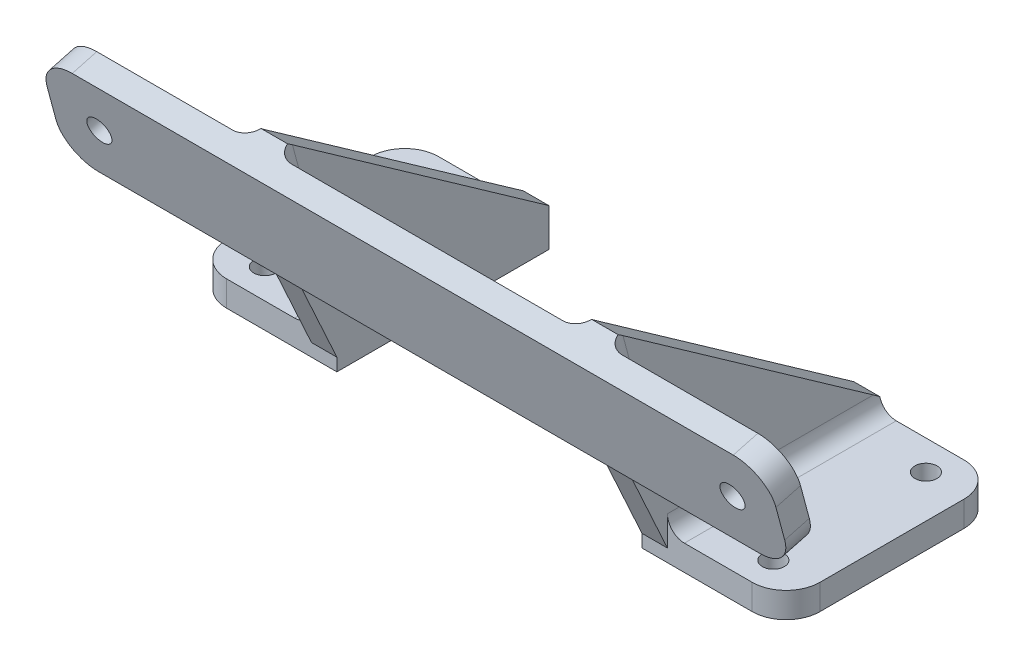
SolidWorks part; units mm, degrees
ref_plane "Front" through (0, 0, 0) normal (0, 0, 1) x (1, 0, 0)
ref_plane "Top" through (0, 0, 0) normal (0, 1, 0) x (1, 0, 0)
ref_plane "Right" through (0, 0, 0) normal (1, 0, 0) x (0, 0, -1)
ref_axis "X" through (-80.9, 0, 0) along (1, 0, 0)
ref_axis "Y" through (0, -50, 0) along (0, 1, 0)
ref_axis "Z" through (0, 0, -80.9) along (0, 0, 1)
sketch "Sketch1" plane through (0, 0, 0) normal (0, 1, 0) x (1, 0, 0)
  line L0 (-26.5, 16) -> (26.5, 16) construction
  line L1 (-35, 28.5) -> (-18, 28.5)
  line L2 (-35, 28.5) -> (-35, 3.5)
  line L3 (-35, 3.5) -> (-18, 3.5)
  line L4 (-18, 28.5) -> (-18, 3.5)
  line L5 (-35, 28.5) -> (-18, 3.5) construction
  line L6 (-35, 3.5) -> (-18, 28.5) construction
  line L7 (18, 28.5) -> (35, 28.5)
  line L8 (18, 28.5) -> (18, 3.5)
  line L9 (18, 3.5) -> (35, 3.5)
  line L10 (35, 28.5) -> (35, 3.5)
  line L11 (18, 28.5) -> (35, 3.5) construction
  line L12 (18, 3.5) -> (35, 28.5) construction
  line L13 (0, 0) -> (0, 16) construction
  point P4 (-26.5, 16)
  point P9 (26.5, 16)
  dimension "D1" = 70
  dimension "D2" = 36
  dimension "D3" = 25
  dimension "D4" = 16
extrude "Boss-Extrude1" add sketch "Sketch1" along normal blind 3
ref_plane "angle 105" through (0, 0, 0) normal (0, 0.2588, -0.9659) x (1, 0, 0)
sketch "Sketch2" plane through (0, 0, 0) normal (0, 0.2588, -0.9659) x (1, 0, 0)
  line L0 (0, -20) -> (0, 0) construction
  line L1 (-43, -14) -> (43, -14)
  line L2 (-43, -14) -> (-43, -26)
  line L3 (-43, -26) -> (43, -26)
  line L4 (43, -14) -> (43, -26)
  line L5 (-43, -14) -> (43, -26) construction
  line L6 (-43, -26) -> (43, -14) construction
  point P4 (0, -20)
  dimension "D1" = 12
  dimension "D2" = 86
  dimension "D3" = 20
extrude "Boss-Extrude2" add sketch "Sketch2" along normal blind 3 separate body
sketch "Sketch3" plane through (0, 0, 0) normal (0, -1, 0) x (1, 0, 0)
  line L0 (0, -16) -> (0, 0) construction
  line L1 (30, -25) -> (-30, -25) construction
  line L2 (30, -25) -> (30, -7) construction
  line L3 (30, -7) -> (-30, -7) construction
  line L4 (-30, -25) -> (-30, -7) construction
  line L5 (30, -25) -> (-30, -7) construction
  line L6 (30, -7) -> (-30, -25) construction
  line L7 (0, -16) -> (18, -16) construction
  line L8 (18, -28.5) -> (18, -3.5) construction
  circle A0 centre (30, -25) radius 1.3
  circle A1 centre (30, -7) radius 1.3
  circle A2 centre (-30, -25) radius 1.3
  circle A3 centre (-30, -7) radius 1.3
  point P4 (0, -16)
  dimension "D2" = 2.6
  dimension "D1" = 18
  dimension "D3" = 60
extrude "Cut-Extrude1" cut sketch "Sketch3" against normal up to next (3 mm away)
sketch "Sketch4" plane through (0, 0, 0) normal (0, -0.2588, 0.9659) x (1, 0, 0)
  line L0 (-37.35, 20) -> (37.35, 20) construction
  line L1 (0, 0) -> (0, 20) construction
  line L2 (-37.35, 20) -> (-43, 20) construction
  line L3 (-43, 14) -> (-43, 26) construction
  circle A0 centre (-37.35, 20) radius 1.44
  circle A1 centre (37.35, 20) radius 1.44
  dimension "D1" = 2.88
  dimension "D2" = 74.7
extrude "Cut-Extrude2" cut sketch "Sketch4" against normal up to next (3 mm away)
sketch "Sketch5" plane through (0, 0, 0) normal (1, 0, 0) x (0, 0, -1)
  line L3 (3.5, 3) -> (28.5, 3)
  line L5 (-3.8315, 25.8905) -> (-0.7257, 14.2994)
  line L6 (-0.7257, 14.2994) -> (-2.1746, 13.9112)
  line L7 (-2.1746, 13.9112) -> (3.5, 1.5)
  line L8 (3.5, 1.5) -> (3.5, 3)
  line L9 (28.5, 3) -> (28.5, 4.5)
  line L10 (28.5, 4.5) -> (-2.3826, 26.2788)
  line L11 (-2.3826, 26.2788) -> (-3.8315, 25.8905)
  line L12 (3.5, 3) -> (3.5, 0) construction
  line L13 (-0.7257, 14.2994) -> (-3.6235, 13.523) construction
  point P4 (-3.8315, 25.9328)
  point P17 (3.5, 1.5)
  point P20 (-2.1746, 13.9112)
  dimension "D1" = 1.5
extrude "Boss-Extrude3" add sketch "Sketch5" along normal blind 3 from surface starting at face at (18, 1.5, -16)
extrude "Boss-Extrude4" add sketch "Sketch5<2>" against normal blind 3 from surface starting at face at (-18, 1.5, -16)
sketch "Sketch5<2>" plane through (0, 0, 0) normal (1, 0, 0) x (0, 0, -1) same geometry as "Sketch5"
fillet "Fillet1" radius 2 6 edges at (-21, 3, -16) (21, 3, -16) (-18, 20.095, 2.2786) (-21, 20.095, 2.2786) (21, 20.095, 2.2786) (18, 20.095, 2.2786)
fillet "Fillet2" radius 4 8 edges at (43, 13.9112, 2.1746) (43, 25.5023, 5.2804) (35, 1.5, -3.5) (35, 1.5, -28.5) (-43, 13.9112, 2.1746) (-43, 25.5023, 5.2804) (-35, 1.5, -3.5) (-35, 1.5, -28.5)
